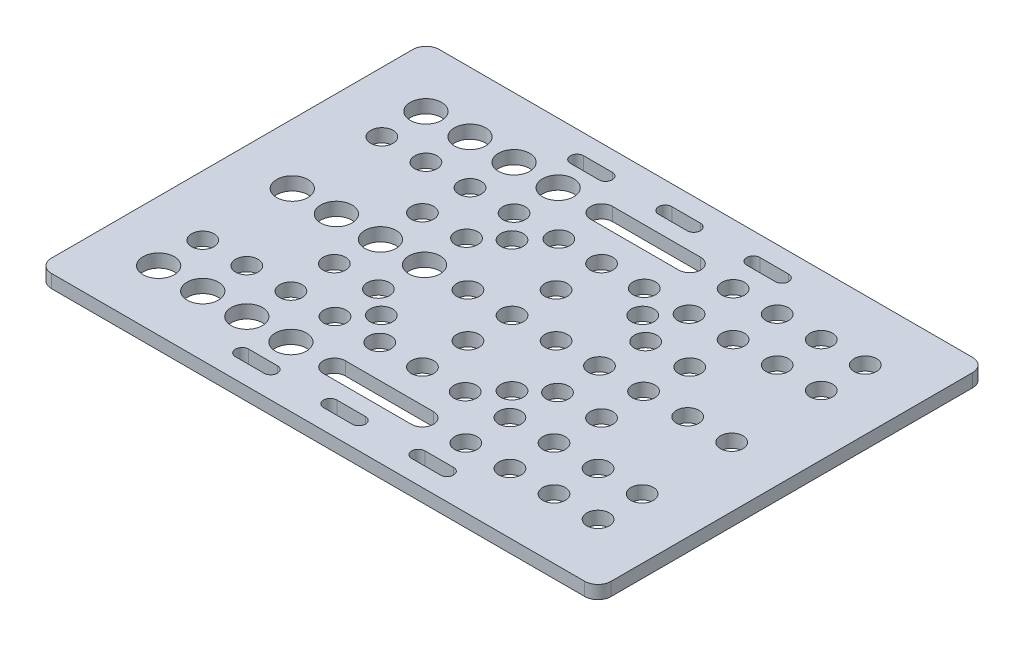
SolidWorks part; units mm, degrees
material "6061-T6 (SS)"
ref_plane "Front Plane" through (0, 0, 0) normal (0, 0, 1) x (1, 0, 0)
ref_plane "Top Plane" through (0, 0, 0) normal (0, 1, 0) x (1, 0, 0)
ref_plane "Right Plane" through (0, 0, 0) normal (1, 0, 0) x (0, 0, -1)
sketch "Sketch1" plane through (0, 0, 0) normal (0, 1, 0) x (1, 0, 0)
  line L0 (0, 0) -> (63.5, 0) construction
  line L1 (60.5, -44) -> (-60.5, -44)
  line L2 (63.5, -41) -> (63.5, 41)
  line L3 (60.5, 44) -> (-60.5, 44)
  line L4 (-63.5, -41) -> (-63.5, 41)
  line L5 (0, 44) -> (0, 0) construction
  line L6 (-49.85, 30.32) -> (-39.85, 30.32) construction
  line L7 (49.85, 30.32) -> (39.85, 30.32) construction
  line L8 (49.85, 0) -> (39.85, 0) construction
  line L9 (10, 30.32) -> (-10, 30.32) construction
  line L10 (10, 27.82) -> (-10, 27.82)
  line L11 (10, 32.82) -> (-10, 32.82)
  line L12 (3.25, 38) -> (-3.25, 38) construction
  line L13 (3.25, 36.5) -> (-3.25, 36.5)
  line L14 (3.25, 39.5) -> (-3.25, 39.5)
  line L15 (-16.75, 38) -> (-23.25, 38) construction
  line L16 (-16.75, 36.5) -> (-23.25, 36.5)
  line L17 (-16.75, 39.5) -> (-23.25, 39.5)
  line L18 (16.75, 38) -> (23.25, 38) construction
  line L19 (16.75, 36.5) -> (23.25, 36.5)
  line L20 (16.75, 39.5) -> (23.25, 39.5)
  line L21 (10, -30.32) -> (-10, -30.32) construction
  line L22 (10, -27.82) -> (-10, -27.82)
  line L23 (10, -32.82) -> (-10, -32.82)
  line L24 (-16.75, -38) -> (-23.25, -38) construction
  line L25 (-16.75, -36.5) -> (-23.25, -36.5)
  line L26 (-16.75, -39.5) -> (-23.25, -39.5)
  line L27 (3.25, -38) -> (-3.25, -38) construction
  line L28 (3.25, -36.5) -> (-3.25, -36.5)
  line L29 (3.25, -39.5) -> (-3.25, -39.5)
  line L30 (16.75, -38) -> (23.25, -38) construction
  line L31 (16.75, -36.5) -> (23.25, -36.5)
  line L32 (16.75, -39.5) -> (23.25, -39.5)
  arc A0 (-60.5, -44) -> (-63.5, -41) centre (-60.5, -41) cw
  arc A1 (60.5, -44) -> (63.5, -41) centre (60.5, -41) ccw
  arc A2 (63.5, 41) -> (60.5, 44) centre (60.5, 41) ccw
  arc A3 (-60.5, 44) -> (-63.5, 41) centre (-60.5, 41) ccw
  circle A4 centre (-39.85, 30.32) radius 3.55
  circle A5 centre (0, 10) radius 2.55
  circle A6 centre (0, 0) radius 2.55
  circle A7 centre (10, 0) radius 2.55
  circle A8 centre (-10, 0) radius 2.55
  circle A9 centre (-49.85, 30.32) radius 3.55
  circle A10 centre (-49.85, 0) radius 3.55
  circle A11 centre (-49.85, -30.32) radius 3.55
  circle A12 centre (-20.32, 10) radius 2.55
  circle A13 centre (-30.32, 10) radius 2.55
  circle A14 centre (-14.825, 14.825) radius 2.55
  circle A15 centre (0, 20.32) radius 2.55
  circle A16 centre (-49.85, 20.32) radius 2.55
  circle A17 centre (-39.85, 20.32) radius 2.55
  circle A18 centre (-29.85, 20.32) radius 2.55
  circle A19 centre (-39.85, 0) radius 3.55
  circle A20 centre (14.825, 14.825) radius 2.55
  circle A21 centre (20.32, 10) radius 2.55
  circle A22 centre (30.32, 10) radius 2.55
  circle A23 centre (39.85, 30.32) radius 2.55
  circle A24 centre (49.85, 30.32) radius 2.55
  circle A25 centre (49.85, 0) radius 2.55
  circle A26 centre (30.32, -10) radius 2.55
  circle A27 centre (49.85, -30.32) radius 2.55
  circle A28 centre (29.85, 30.32) radius 2.55
  circle A29 centre (20.32, -10) radius 2.55
  circle A30 centre (0, -10) radius 2.55
  circle A31 centre (14.825, -14.825) radius 2.55
  circle A32 centre (-29.85, 0) radius 3.55
  circle A33 centre (-19.85, 20.32) radius 2.55
  circle A34 centre (-9.69, 20.32) radius 2.55
  circle A35 centre (9.69, 20.32) radius 2.55
  circle A36 centre (-19.85, 0) radius 3.55
  circle A37 centre (-14.825, -14.825) radius 2.55
  circle A38 centre (-20.32, -10) radius 2.55
  circle A39 centre (-30.32, -10) radius 2.55
  circle A40 centre (-29.85, 30.32) radius 3.55
  circle A41 centre (-19.85, 30.32) radius 3.55
  circle A42 centre (19.85, 30.32) radius 2.55
  circle A43 centre (19.85, 20.32) radius 2.55
  circle A44 centre (29.85, 20.32) radius 2.55
  circle A45 centre (39.85, 20.32) radius 2.55
  circle A46 centre (49.85, 20.32) radius 2.55
  circle A47 centre (39.85, 0) radius 2.55
  circle A48 centre (29.85, 0) radius 2.55
  circle A49 centre (19.85, 0) radius 2.55
  circle A50 centre (19.85, -30.32) radius 2.55
  circle A51 centre (29.85, -30.32) radius 2.55
  circle A52 centre (0, -20.32) radius 2.55
  circle A53 centre (39.85, -30.32) radius 2.55
  circle A54 centre (49.85, -20.32) radius 2.55
  circle A55 centre (39.85, -20.32) radius 2.55
  circle A56 centre (29.85, -20.32) radius 2.55
  circle A57 centre (19.85, -20.32) radius 2.55
  circle A58 centre (9.69, -20.32) radius 2.55
  circle A59 centre (-9.69, -20.32) radius 2.55
  circle A60 centre (-19.85, -20.32) radius 2.55
  circle A61 centre (-29.85, -20.32) radius 2.55
  circle A62 centre (-39.85, -20.32) radius 2.55
  circle A63 centre (-49.85, -20.32) radius 2.55
  circle A64 centre (-19.85, -30.32) radius 3.55
  circle A65 centre (-29.85, -30.32) radius 3.55
  circle A66 centre (-39.85, -30.32) radius 3.55
  arc A67 (10, 27.82) -> (10, 32.82) centre (10, 30.32) ccw
  arc A68 (-10, 32.82) -> (-10, 27.82) centre (-10, 30.32) ccw
  arc A69 (3.25, 36.5) -> (3.25, 39.5) centre (3.25, 38) ccw
  arc A70 (-3.25, 39.5) -> (-3.25, 36.5) centre (-3.25, 38) ccw
  arc A71 (-16.75, 36.5) -> (-16.75, 39.5) centre (-16.75, 38) ccw
  arc A72 (-23.25, 39.5) -> (-23.25, 36.5) centre (-23.25, 38) ccw
  arc A73 (16.75, 36.5) -> (16.75, 39.5) centre (16.75, 38) cw
  arc A74 (23.25, 39.5) -> (23.25, 36.5) centre (23.25, 38) cw
  arc A75 (10, -27.82) -> (10, -32.82) centre (10, -30.32) cw
  arc A76 (-10, -32.82) -> (-10, -27.82) centre (-10, -30.32) cw
  arc A77 (-16.75, -36.5) -> (-16.75, -39.5) centre (-16.75, -38) cw
  arc A78 (-23.25, -39.5) -> (-23.25, -36.5) centre (-23.25, -38) cw
  arc A79 (3.25, -36.5) -> (3.25, -39.5) centre (3.25, -38) cw
  arc A80 (-3.25, -39.5) -> (-3.25, -36.5) centre (-3.25, -38) cw
  arc A81 (16.75, -36.5) -> (16.75, -39.5) centre (16.75, -38) ccw
  arc A82 (23.25, -39.5) -> (23.25, -36.5) centre (23.25, -38) ccw
  point P0 (0, 0)
  point P149 (0, 30.32)
  point P156 (0, 38)
  point P162 (-20, 38)
  point P170 (20, 38)
  point P177 (0, -30.32)
  point P184 (-20, -38)
  point P191 (0, -38)
  point P198 (20, -38)
  dimension "D2" = 3
  dimension "D3" = 5.1
  dimension "D5" = 7.1
  dimension "D7" = 4
  dimension "D10" = 10
  dimension "D19" = 10
  dimension "D1" = 88
  dimension "D4" = 10
  dimension "D6" = 60.64
  dimension "D8" = 13.65
  dimension "D9" = 127
  dimension "D11" = 10
  dimension "D12" = 4
  dimension "D13" = 10
  dimension "D14" = 10
  dimension "D15" = 20.32
  dimension "D16" = 99.7
  dimension "D17" = 4
  dimension "D18" = 10
  dimension "D20" = 29.65
  dimension "D21" = 29.65
  dimension "D22" = 10.16
  dimension "D24" = 10
  dimension "D25" = 5
  dimension "D26" = 20
  dimension "D27" = 6.5
  dimension "D28" = 3
  dimension "D29" = 20
  dimension "D30" = 60.64
  dimension "D31" = 76
  dimension "D23" = 4
extrude "Boss-Extrude1" add sketch "Sketch1" along normal blind 3
ref_plane "Plane1" through (0, 0, 0) normal (0, 0, 1) x (1, 0, 0)
ref_plane "Plane2" through (-63.5, 0, 0) normal (-1, 0, 0) x (0, 0, 1)
